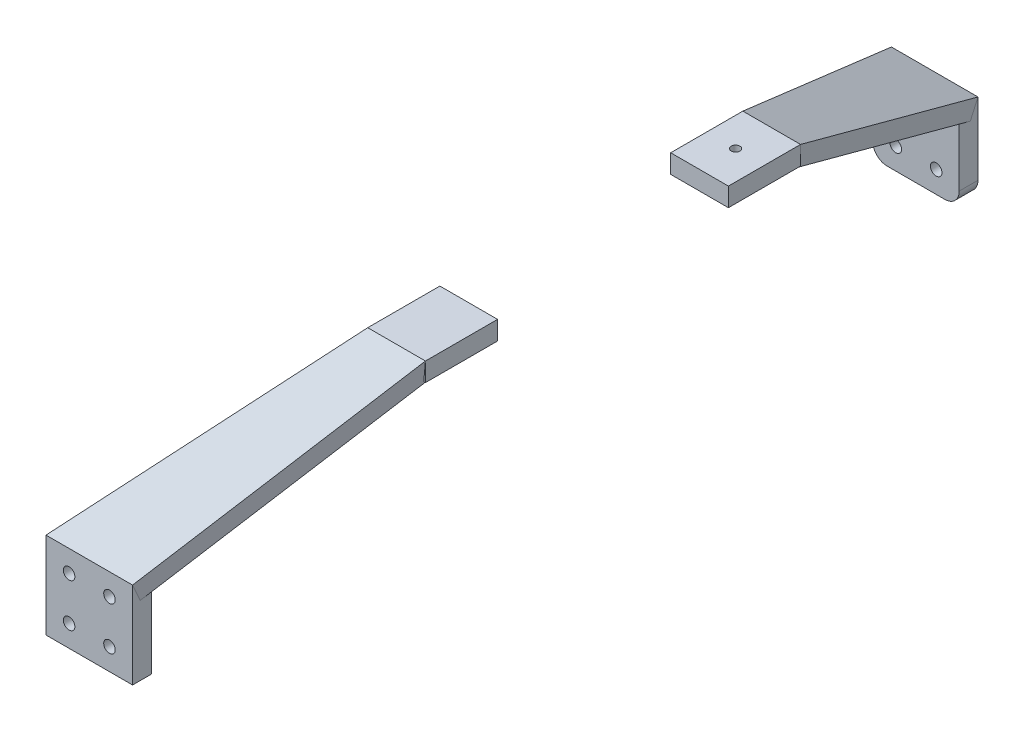
SolidWorks part; units mm, degrees
note: The reader was unsure of these and kept them because the rebuilt part matched: shared geometry of "Szkic5<7>".
material "1.0045 (S355JR)"
ref_plane "Płaszczyzna przednia" through (0, 0, 0) normal (0, 0, 1) x (1, 0, 0)
ref_plane "Płaszczyzna górna" through (0, 0, 0) normal (0, 1, 0) x (1, 0, 0)
ref_plane "Płaszczyzna prawa" through (0, 0, 0) normal (1, 0, 0) x (0, 0, -1)
sketch "Szkic1" plane through (0, 0, 0) normal (0, 0, 1) x (1, 0, 0)
  line L1 (-30, -30) -> (30, -30)
  line L2 (-30, -30) -> (-30, 30)
  line L3 (-30, 30) -> (30, 30)
  line L4 (30, -30) -> (30, 30)
  line L5 (-30, -30) -> (30, 30) construction
  line L6 (-30, 30) -> (30, -30) construction
  point P0 (0, 0)
  dimension "D1" = 60
  dimension "D2" = 60
extrude "Dodanie-wyciągnięcie1" add sketch "Szkic1" along normal blind 13
hole_wizard "Otwory ustalające Ø8.0mm1" positions "Szkic2" profile "Szkic3" hole size "Ø8.0" standard "ISO" end condition up to next
sketch "Szkic2" plane through (0, 0, 13) normal (0, 0, 1) x (1, 0, 0)
  point P0 (14, 15)
  point P2 (-14, 15)
  point P4 (-14, -15)
  point P6 (14, -15)
  dimension "D1" = 28
  dimension "D2" = 30
  dimension "D3" = 14
  dimension "D4" = 15
sketch "Szkic3" plane through (14, 15, 13) normal (1, 0, 0) x (0, -1, 0)
  line L0 (0, 0) -> (0, 13)
  line L1 (0, 13) -> (4, 13)
  line L2 (4, 13) -> (4, 0)
  line L5 (4, 0) -> (0, 0)
  line L11 (0, -6.35) -> (0, 107.95) construction
  dimension "Średnica otworu na wylot" = 8
  dimension "Głębokość otworu na wylot" = 13
ref_plane "Płaszczyzna1" through (0, 0, -150) normal (0, 0, -1) x (-1, 0, 0)
sketch "Szkic4" plane through (0, 30, 0) normal (0, 1, 0) x (1, 0, 0)
  line L4 (30, 0) -> (-30, 0)
  line L5 (-30, 0) -> (-30, -13)
  line L6 (-30, -13) -> (30, -13)
  line L7 (30, -13) -> (30, 0)
  line L8 (30, 0) -> (-30, 0)
  line L9 (-30, 0) -> (-30, -13)
  line L10 (-30, -13) -> (30, -13)
  line L11 (30, -13) -> (30, 0)
  dimension "D1" = 0
sketch "Szkic5" plane through (0, 0, -150) normal (0, 0, -1) x (-1, 0, 0)
  line L0 (-30, 30) -> (30, 30) construction
  line L1 (-70, 90) -> (-30, 90)
  line L2 (-70, 90) -> (-70, 103)
  line L3 (-70, 103) -> (-30, 103)
  line L4 (-30, 90) -> (-30, 103)
  line L5 (-70, 90) -> (-30, 103) construction
  line L6 (-70, 103) -> (-30, 90) construction
  line L7 (30, 30) -> (30, -30) construction
  point P0 (-50, 96.5)
  dimension "D1" = 13
  dimension "D2" = 40
  dimension "D3" = 60
  dimension "D4" = 60
loft "Wyciągnięcie po profilach1" [suppressed] add profiles "Szkic4", "Szkic5"
sketch "Szkic6" [suppressed] plane through (0, 0, -150) normal (0, 0, -1) x (-1, 0, 0)
  line L4 (-30, 140) -> (-30, 155)
  line L5 (-30, 155) -> (-70, 155)
  line L6 (-70, 155) -> (-70, 140)
  line L7 (-70, 140) -> (-30, 140)
  line L8 (-30, 140) -> (-30, 155)
  line L9 (-30, 155) -> (-70, 155)
  line L10 (-70, 155) -> (-70, 140)
  line L11 (-70, 140) -> (-30, 140)
  dimension "D1" = 0
extrude "Dodanie-wyciągnięcie2" [suppressed] add sketch "Szkic6" along normal blind 20
fillet "Zaokrąglenie1" [suppressed] radius 5
fillet "Zaokrąglenie2" [suppressed] radius 5
ref_plane "Płaszczyzna2" [suppressed] through (0, 0, -280) normal (0, 0, -1) x (-1, 0, 0)
mirror "Lustro1" [suppressed] about plane through (0, 0, -280) normal (0, 0, -1)
ref_plane "Płaszczyzna3" through (0, 29.8375, 13.3628) normal (0, 0.9127, 0.4087) x (1, 0, 0)
sketch "Szkic7" plane through (0, 29.8375, 13.3628) normal (0, 0.9127, 0.4087) x (1, 0, 0)
  line L0 (30, 0.3975) -> (70, 178.9976)
  line L1 (70, 178.9976) -> (30, 178.9976)
  line L2 (30, 178.9976) -> (-30, 0.3975)
  line L3 (-30, 0.3975) -> (30, 0.3975)
extrude "Dodanie-wyciągnięcie3" add sketch "Szkic7" against normal blind 13 contours L2 L3 L0 L1
extrude "Dodanie-wyciągnięcie6" add sketch "Szkic5<7>" along normal blind 50 contours L2 L3 L4 L1
sketch "Szkic5<7>" plane through (0, 0, -150) normal (0, 0, -1) x (-1, 0, 0) same geometry as "Szkic5"
mirror "Lustro3" about plane through (0, 0, -280) normal (0, 0, -1) of bodies 111
fillet "Zaokrąglenie3" radius 10 1 edges at (30, -30, -566.5)
fillet "Zaokrąglenie4" radius 10 1 edges at (-30, -30, -566.5)
hole_wizard "Otwory ustalające Ø6.0mm1" positions "Szkic8" profile "Szkic9" hole size "Ø6.0" standard "ISO" end condition through all
sketch "Szkic8" plane through (0, 103, 0) normal (0, 1, 0) x (1, 0, 0)
  line L0 (50, 410) -> (50, 360) construction
  line L1 (70, 410) -> (30, 410) construction
  line L2 (70, 360) -> (30, 360) construction
  line L4 (70, 385) -> (30, 385) construction
  line L5 (70, 360) -> (70, 410) construction
  line L6 (30, 360) -> (30, 410) construction
  point P0 (50, 385)
  point P19 (0, 0)
sketch "Szkic9" plane through (50, 103, -385) normal (1, 0, 0) x (0, 0, 1)
  line L0 (0, 0) -> (0, 133)
  line L1 (0, 133) -> (3, 133)
  line L2 (3, 133) -> (3, 0)
  line L5 (3, 0) -> (0, 0)
  line L11 (0, -6.35) -> (0, 107.95) construction
  dimension "Średnica otworu na wylot" = 6
  dimension "Głębokość otworu na wylot" = 133
